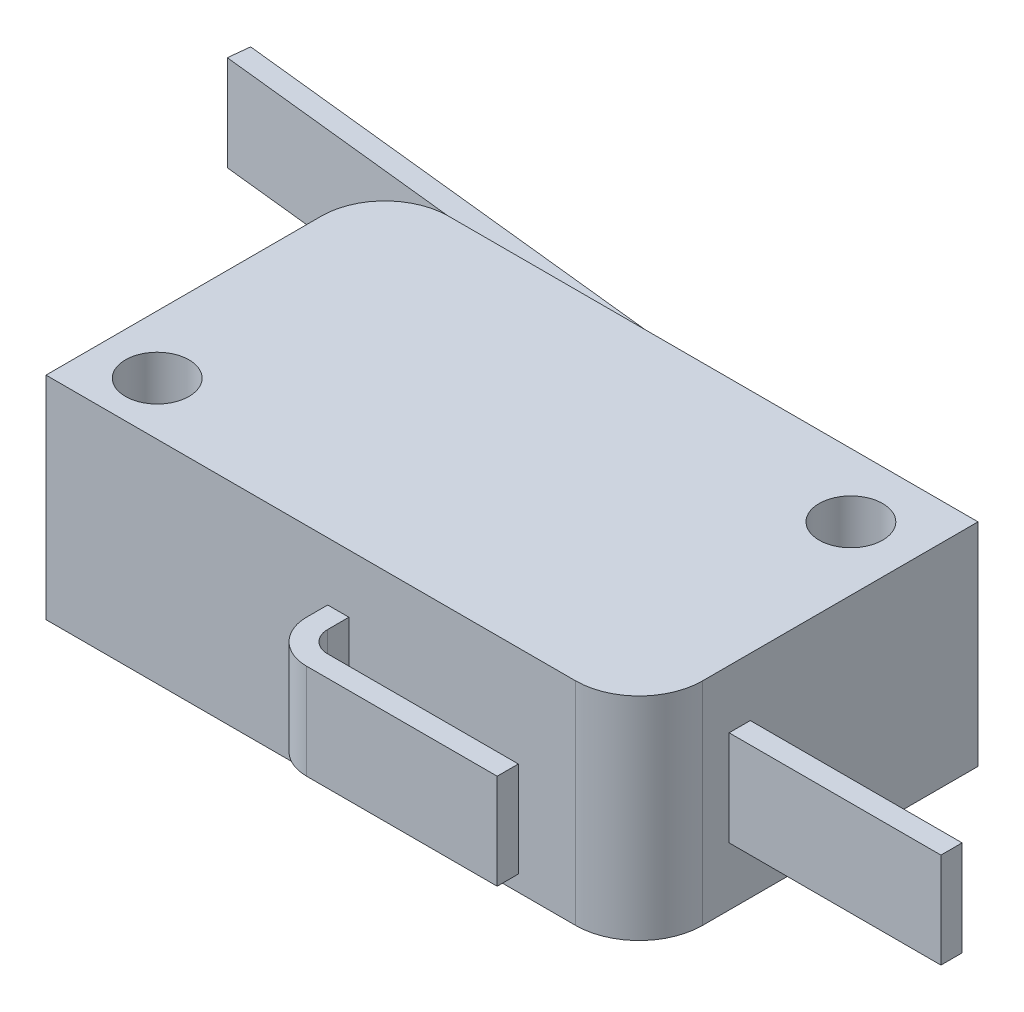
SolidWorks part; units mm, degrees
ref_plane "Front Plane" through (0, 0, 0) normal (0, 0, 1) x (1, 0, 0)
ref_plane "Top Plane" through (0, 0, 0) normal (0, 1, 0) x (1, 0, 0)
ref_plane "Right Plane" through (0, 0, 0) normal (1, 0, 0) x (0, 0, -1)
sketch "Sketch1" plane through (0, 0, 0) normal (0, 1, 0) x (1, 0, 0)
  line L0 (-25.3388, 13) -> (1.6071, 10.0962)
  line L1 (-14, -8) -> (11, -8)
  line L2 (-14, -8) -> (-14, 5)
  line L3 (-11, 8) -> (14, 8)
  line L4 (14, -5) -> (14, 8)
  line L5 (-14, -8) -> (14, 8) construction
  line L6 (-14, 8) -> (14, -8) construction
  line L7 (2.5, 9.102) -> (2.5, 8)
  line L8 (0.3, -8) -> (0.3, -9)
  line L9 (1.3, -10) -> (10.3, -10)
  line L10 (14, -2.75) -> (24, -2.75)
  circle A0 centre (11, 5) radius 1.5
  circle A1 centre (-11.25, -5.5) radius 1.5
  arc A2 (1.6071, 10.0962) -> (2.5, 9.102) centre (1.5, 9.102) cw
  arc A3 (11, -8) -> (14, -5) centre (11, -5) ccw
  arc A4 (-14, 5) -> (-11, 8) centre (-11, 5) cw
  arc A5 (0.3, -9) -> (1.3, -10) centre (1.3, -9) ccw
  point P0 (0, 0)
  point P15 (2.5, 10)
  point P27 (2.5, -10.1059)
  point P30 (0.3, -10)
  dimension "D3" = 3
  dimension "D12" = 1
  dimension "D13" = 3
  dimension "D19" = 1
  dimension "D1" = 28
  dimension "D2" = 16
  dimension "D4" = 22.25
  dimension "D5" = 10.5
  dimension "D6" = 3
  dimension "D7" = 3
  dimension "D8" = 2
  dimension "D9" = 5
  dimension "D10" = 28
  dimension "D11" = 11.5
  dimension "D14" = 2
  dimension "D15" = 10
  dimension "D16" = 10
  dimension "D17" = 14.3
  dimension "D18" = 10.75
extrude "Boss-Extrude1" add sketch "Sketch1" along normal mid plane 10 contours A4 L2 L1 A3 L4 L3 A1 A0 region at (0.0041, 0, -0.0082)
extrude "Extrude-Thin1" add sketch "Sketch1<3>" along normal mid plane 4.5 thin contours L0 A2 L7 | L8 A5 L9 | L10 thin type one direction wall 1
sketch "Sketch1<3>" plane through (0, 0, 0) normal (0, 1, 0) x (1, 0, 0) same geometry as "Sketch1"
